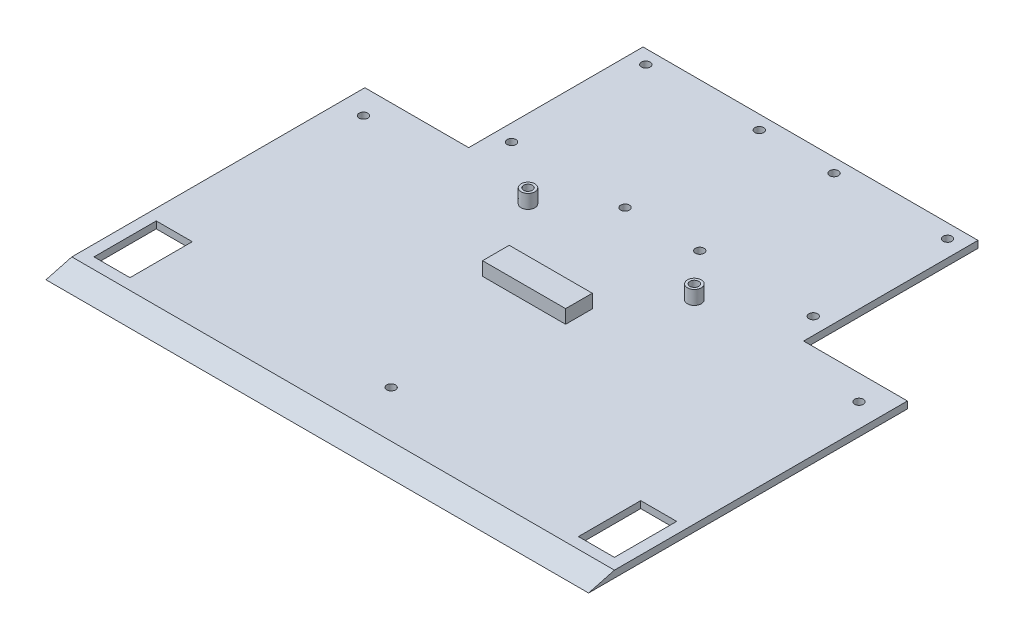
SolidWorks part; units mm, degrees
ref_plane "Alzado" through (0, 0, 0) normal (0, 0, 1) x (1, 0, 0)
ref_plane "Planta" through (0, 0, 0) normal (0, 1, 0) x (1, 0, 0)
ref_plane "Vista lateral" through (0, 0, 0) normal (1, 0, 0) x (0, 0, -1)
sketch "Croquis1" plane through (0, 0, 0) normal (1, 0, 0) x (0, 0, -1)
  line L0 (0, 0) -> (178.17, 0)
  line L1 (178.17, 0) -> (178.17, 2.5)
  line L2 (178.17, 2.5) -> (9.3301, 2.5)
  line L3 (0, 0) -> (9.3301, 2.5)
  dimension "D1" = 178.17
  dimension "D2" = 2.5
  dimension "D3" = 165
extrude "Saliente-Extruir1" add sketch "Croquis1" along normal blind 196
sketch "Croquis2" plane through (0, 0, 0) normal (0, -1, 0) x (-1, 0, 0)
  line L1 (-37.5, 115.1801) -> (0, 115.1801)
  line L2 (-37.5, 115.1801) -> (-37.5, 178.17)
  line L3 (-37.5, 178.17) -> (0, 178.17)
  line L4 (0, 115.1801) -> (0, 178.17)
  line L5 (-37.5, 115.1801) -> (0, 178.17) construction
  line L6 (-37.5, 178.17) -> (0, 115.1801) construction
  line L7 (-158.5, 115.1801) -> (-196, 115.1801)
  line L8 (-158.5, 115.1801) -> (-158.5, 178.17)
  line L9 (-158.5, 178.17) -> (-196, 178.17)
  line L10 (-196, 115.1801) -> (-196, 178.17)
  line L11 (-158.5, 115.1801) -> (-196, 178.17) construction
  line L12 (-158.5, 178.17) -> (-196, 115.1801) construction
  point P4 (-18.75, 146.6751)
  point P11 (-177.25, 146.6751)
extrude "Cortar-Extruir1" cut sketch "Croquis2" against normal up to next
sketch "Croquis4" plane through (0, 2.5, 0) normal (0, 1, 0) x (1, 0, 0)
  line L7 (4, 13.3301) -> (17, 13.3301)
  line L8 (4, 13.3301) -> (4, 35.8301)
  line L9 (4, 35.8301) -> (17, 35.8301)
  line L10 (17, 13.3301) -> (17, 35.8301)
  line L11 (4, 13.3301) -> (17, 35.8301) construction
  line L12 (4, 35.8301) -> (17, 13.3301) construction
  point P9 (10.5, 24.5801)
  dimension "D3" = 22.5
  dimension "D4" = 13
extrude "Cortar-Extruir2" cut sketch "Croquis4" against normal up to next
ref_plane "Plano1" through (98, 0, 0) normal (1, 0, 0) x (0, 0, -1)
mirror "Simetría1" about plane through (98, 0, 0) normal (1, 0, 0) of "Cortar-Extruir2"
sketch "Sketch1" plane through (0, 2.5, 0) normal (0, 1, 0) x (1, 0, 0)
  circle A0 centre (187.5, 106.1801) radius 1.585
  circle A1 centre (8.5, 106.1801) radius 1.585
extrude "Cut-Extrude1" cut sketch "Sketch1" against normal up to next
sketch "Sketch2" plane through (0, 2.5, 0) normal (0, 1, 0) x (1, 0, 0)
  circle A0 centre (98.5, 26.1801) radius 1.585
extrude "Cut-Extrude2" cut sketch "Sketch2" against normal up to next
sketch "Sketch3" plane through (0, 2.5, 0) normal (0, 1, 0) x (1, 0, 0)
  circle A0 centre (111.5, 124.67) radius 1.585
  circle A1 centre (152.5, 124.67) radius 1.585
  circle A2 centre (152.5, 173.17) radius 1.585
  circle A3 centre (111.5, 173.17) radius 1.585
  circle A4 centre (84.5, 173.17) radius 1.585
  circle A5 centre (43.5, 173.17) radius 1.585
  circle A6 centre (43.5, 124.67) radius 1.585
  circle A7 centre (84.5, 124.67) radius 1.585
extrude "Cut-Extrude3" cut sketch "Sketch3" against normal up to next
sketch "Sketch4" plane through (0, 2.5, 0) normal (0, 1, 0) x (1, 0, 0)
  circle A0 centre (125.8764, 108.3369) radius 1.6
  circle A1 centre (65.7764, 108.3369) radius 1.6
  circle A2 centre (65.7764, 108.3369) radius 2.5
  circle A3 centre (125.8764, 108.3369) radius 2.5
  dimension "D1" = 5
  dimension "D2" = 5
extrude "Boss-Extrude1" add sketch "Sketch4" along normal blind 5
sketch "Sketch5" plane through (0, 2.5, 0) normal (0, 1, 0) x (1, 0, 0)
  line L1 (80.272, 87.0616) -> (110.272, 87.0616)
  line L2 (80.272, 87.0616) -> (80.272, 77.4239)
  line L3 (80.272, 77.4239) -> (110.272, 77.4239)
  line L4 (110.272, 87.0616) -> (110.272, 77.4239)
  line L5 (80.272, 87.0616) -> (110.272, 77.4239) construction
  line L6 (80.272, 77.4239) -> (110.272, 87.0616) construction
  point P4 (96.9958, 82.487)
extrude "Boss-Extrude2" add sketch "Sketch5" along normal blind 4.9
sketch "Sketch6" plane through (0, 2.5, 0) normal (0, 1, 0) x (1, 0, 0)
  circle A0 centre (125.8764, 108.3369) radius 1.6
  circle A1 centre (65.7764, 108.3369) radius 1.6
extrude "Cut-Extrude4" cut sketch "Sketch6" against normal blind 4.9
